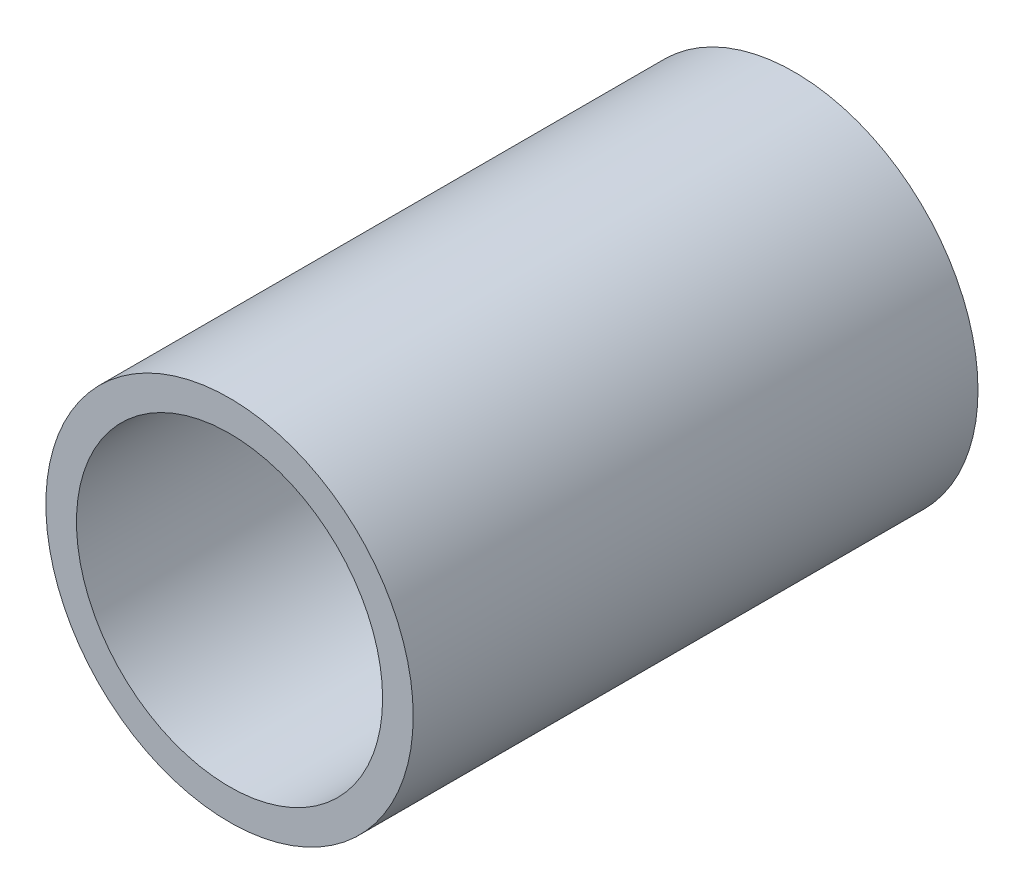
SolidWorks part; units mm, degrees
material "PLA 50%"
ref_plane "Front Plane" through (0, 0, 0) normal (0, 0, 1) x (1, 0, 0)
ref_plane "Top Plane" through (0, 0, 0) normal (0, 1, 0) x (1, 0, 0)
ref_plane "Right Plane" through (0, 0, 0) normal (1, 0, 0) x (0, 0, -1)
ref_axis "X" through (-88.99, 0, 0) along (1, 0, 0)
ref_axis "Y" through (0, 55, 0) along (0, -1, 0)
ref_axis "Z" through (0, 0, -88.99) along (0, 0, 1)
sketch "Sketch1" plane through (0, 0, 0) normal (0, 0, 1) x (1, 0, 0)
  circle A0 centre (0, 0) radius 5
  circle A1 centre (0, 0) radius 6
  dimension "D1" = 10
  dimension "D2" = 12
extrude "Boss-Extrude1" add sketch "Sketch1" against normal up to surface (18.4488 mm away)
